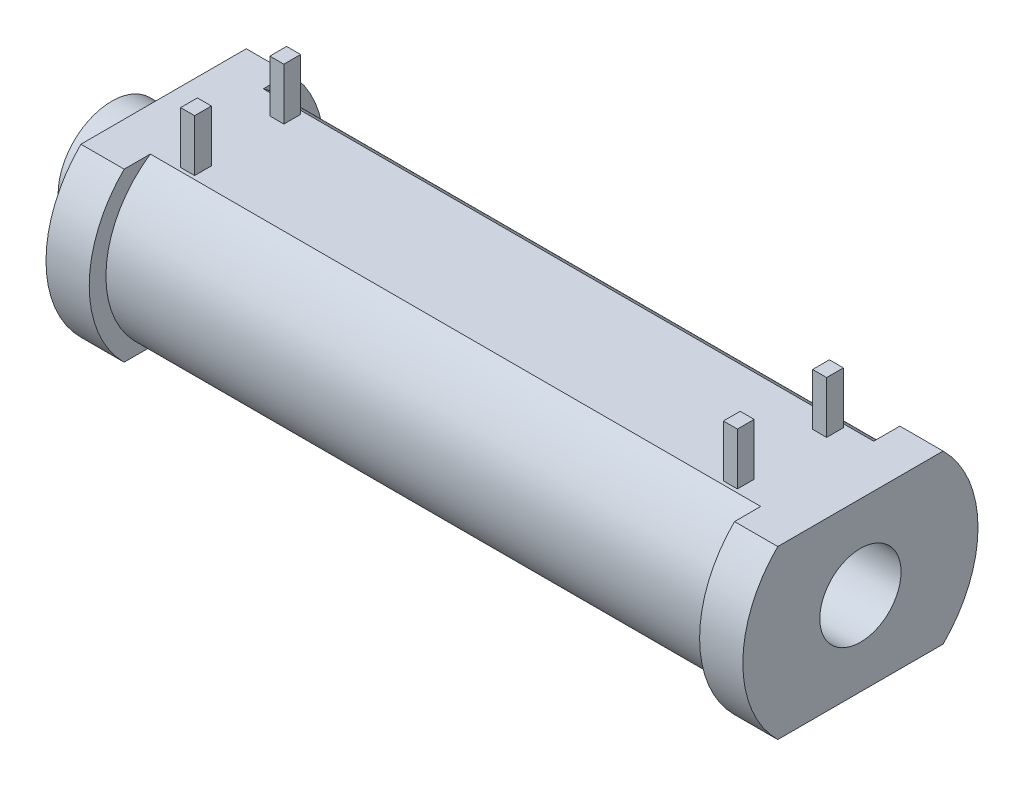
SolidWorks part; units mm, degrees
ref_plane "Front Plane" through (0, 0, 0) normal (0, 0, 1) x (1, 0, 0)
ref_plane "Top Plane" through (0, 0, 0) normal (0, 1, 0) x (1, 0, 0)
ref_plane "Right Plane" through (0, 0, 0) normal (1, 0, 0) x (0, 0, -1)
sketch "Sketch2" plane through (0, 0, 0) normal (0, 1, 0) x (1, 0, 0)
  line L0 (79.2012, 0) -> (0, 0) construction
  line L1 (0, 0) -> (-62.3416, 0) construction
  line L2 (-17.65, 5.835) -> (17.65, 5.835)
  line L3 (17.65, 5.835) -> (17.65, 6.8)
  line L4 (17.65, 6.8) -> (20.15, 6.8)
  line L5 (20.15, 6.8) -> (20.15, 0)
  line L6 (0, 0) -> (0, 5.835) construction
  line L7 (-20.15, 6.8) -> (-20.15, 0)
  line L8 (-17.65, 6.8) -> (-20.15, 6.8)
  line L9 (-17.65, 5.835) -> (-17.65, 6.8)
  line L10 (20.15, 0) -> (-20.15, 0)
  dimension "D1" = 5.835
  dimension "D2" = 6.8
  dimension "D3" = 17.65
  dimension "D4" = 2.5
revolve "Revolve1" add sketch "Sketch2" angle 360 about L10
ref_plane "Plane1" through (12.7, 0, 0) normal (1, 0, 0) x (0, 0, -1)
sketch "Sketch3" plane through (-20.15, 0, 0) normal (-1, 0, 0) x (0, 0, 1)
  circle A0 centre (0, 0) radius 2.35
  dimension "D1" = 4.7
extrude "Cut-Extrude1" cut sketch "Sketch3" against normal up to next
sketch "Sketch4" plane through (0, 0, 0) normal (0, 0, 1) x (1, 0, 0)
  line L0 (17.65, 5.835) -> (-17.65, 5.835) construction
  line L1 (-25.4899, 4.835) -> (25.4899, 4.835)
  line L2 (-25.4899, 4.835) -> (-25.4899, 6.835)
  line L3 (-25.4899, 6.835) -> (25.4899, 6.835)
  line L4 (25.4899, 4.835) -> (25.4899, 6.835)
  line L5 (-25.4899, 4.835) -> (25.4899, 6.835) construction
  line L6 (-25.4899, 6.835) -> (25.4899, 4.835) construction
  line L7 (-17.65, -5.835) -> (17.65, -5.835) construction
  line L8 (-27.5176, -4.835) -> (27.5176, -4.835)
  line L9 (-27.5176, -4.835) -> (-27.5176, -6.835)
  line L10 (-27.5176, -6.835) -> (27.5176, -6.835)
  line L11 (27.5176, -4.835) -> (27.5176, -6.835)
  line L12 (-27.5176, -4.835) -> (27.5176, -6.835) construction
  line L13 (-27.5176, -6.835) -> (27.5176, -4.835) construction
  point P0 (0, 5.835)
  point P7 (0, -5.835)
  dimension "D1" = 1
  dimension "D2" = 1
extrude "Cut-Extrude2" cut sketch "Sketch4" against normal through all and the other way through all
sketch "Sketch5" plane through (0, 4.835, 0) normal (0, 1, 0) x (1, 0, 0)
  line L0 (-16.35, 9.9774) -> (-16.35, -9.9774) construction
  line L1 (-17.44, 9.9774) -> (17.44, 9.9774) construction
  line L2 (-17.44, 9.9774) -> (-17.44, -9.9774) construction
  line L3 (-17.44, -9.9774) -> (17.44, -9.9774) construction
  line L4 (17.44, 9.9774) -> (17.44, -9.9774) construction
  line L5 (-17.44, 9.9774) -> (17.44, -9.9774) construction
  line L6 (-17.44, -9.9774) -> (17.44, 9.9774) construction
  line L7 (-15.04, 9.9774) -> (-15.04, -9.9774) construction
  line L8 (0, 0) -> (7.3074, 0) construction
  line L9 (-16.35, -1.845) -> (-15.04, -1.845) construction
  line L10 (-16.35, -1.845) -> (-16.35, -3.565) construction
  line L11 (-16.35, -3.565) -> (-15.04, -3.565) construction
  line L12 (-15.04, -1.845) -> (-15.04, -3.565) construction
  line L13 (-16.1, -2.095) -> (-15.29, -2.095)
  line L14 (-16.1, -2.095) -> (-16.1, -3.065)
  line L15 (-16.1, -3.065) -> (-15.29, -3.065)
  line L16 (-15.29, -2.095) -> (-15.29, -3.065)
  line L17 (0, 0) -> (0, 7.1934) construction
  line L18 (15.29, -2.095) -> (15.29, -3.065)
  line L19 (16.1, -3.065) -> (15.29, -3.065)
  line L20 (16.1, -2.095) -> (16.1, -3.065)
  line L21 (16.1, -2.095) -> (15.29, -2.095)
  line L22 (16.1, 2.095) -> (15.29, 2.095)
  line L23 (16.1, 2.095) -> (16.1, 3.065)
  line L24 (16.1, 3.065) -> (15.29, 3.065)
  line L25 (15.29, 2.095) -> (15.29, 3.065)
  line L26 (-15.29, 2.095) -> (-15.29, 3.065)
  line L27 (-16.1, 3.065) -> (-15.29, 3.065)
  line L28 (-16.1, 2.095) -> (-16.1, 3.065)
  line L29 (-16.1, 2.095) -> (-15.29, 2.095)
  point P0 (0, 0)
  dimension "D1" = 34.88
  dimension "D2" = 1.09
  dimension "D3" = 1.31
  dimension "D4" = 1.72
  dimension "D5" = 0.5
  dimension "D6" = 0.5
  dimension "D7" = 0.5
  dimension "D8" = 0.5
extrude "Boss-Extrude1" add sketch "Sketch5" along normal blind 3
sketch "Sketch6" plane through (-20.15, 0, 0) normal (-1, 0, 0) x (0, 0, 1)
  circle A0 centre (0, 0) radius 2.35
  circle A1 centre (0, 0) radius 3.1
  dimension "D1" = 0.75
extrude "Boss-Extrude2" add sketch "Sketch6" along normal blind 3
fillet "Fillet1" radius 1 1 edges at (-20.15, 0, 3.1)
